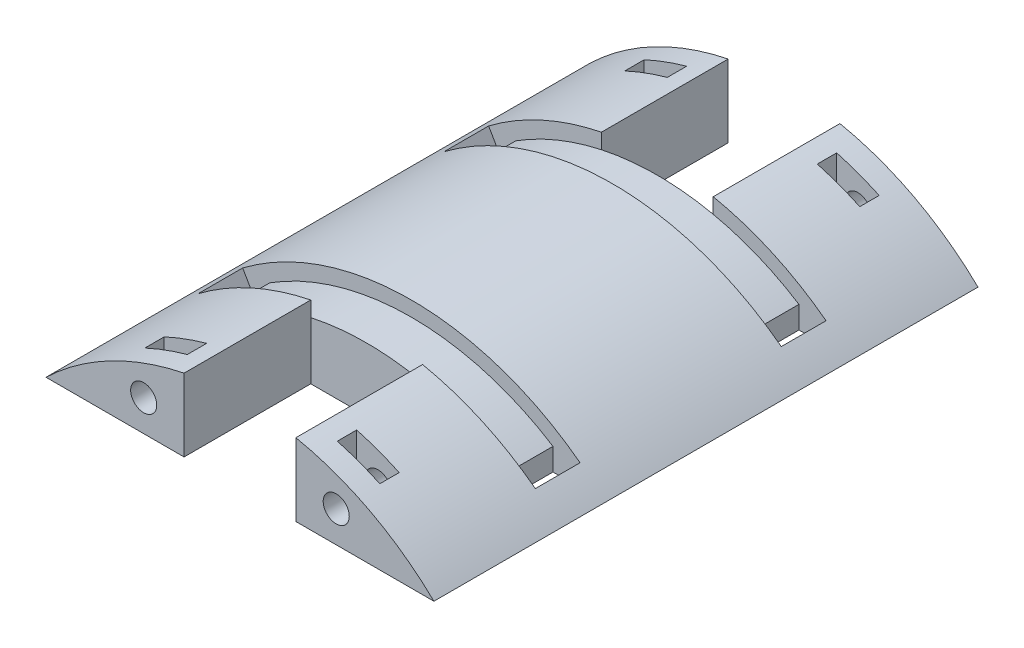
SolidWorks part; units mm, degrees
ref_plane "Plan de face" through (0, 0, 0) normal (0, 0, 1) x (1, 0, 0)
ref_plane "Plan de dessus" through (0, 0, 0) normal (0, 1, 0) x (1, 0, 0)
ref_plane "Plan de droite" through (0, 0, 0) normal (1, 0, 0) x (0, 0, -1)
sketch "Esquisse3" plane through (0, 0, 0) normal (0, 0, 1) x (1, 0, 0)
  line L0 (-13.0767, 27) -> (-26.024, 27)
  line L1 (13.0767, 27) -> (26.024, 27)
  line L2 (-13.0767, 27) -> (13.0767, 27)
  line L3 (-26.024, 27) -> (26.024, 27) construction
  line L4 (-26.024, 27) -> (-26.024, 0) construction
  line L5 (-26.024, 0) -> (26.024, 0) construction
  line L6 (26.024, 27) -> (26.024, 0) construction
  line L7 (8.9994, 41.4168) -> (9.1038, 41.3823)
  circle A0 centre (0, 0) radius 37.5 construction
  circle A1 centre (0, 0) radius 30 construction
  arc A2 (-26.024, 27) -> (26.024, 27) centre (0, 0) cw
  point P5 (0, 0)
  point P15 (0, 27)
  dimension "D1" = 75
  dimension "D2" = 60
  dimension "D4" = 27
extrude "Boss.-Extru.2" add sketch "Esquisse3" along normal blind 73 contours A2 L0 L2 L1 region at (0, 31.2549, 0)
sketch "Esquisse7" plane through (0, 0, 73) normal (0, 0, 1) x (1, 0, 0)
  line L0 (0, 33.75) -> (0, 0) construction
  line L1 (0, 0) -> (-12.9156, 31.1809) construction
  line L2 (0, 0) -> (12.9156, 31.1809) construction
  line L3 (-30, 0) -> (-37.5, 0) construction
  circle A0 centre (0, 0) radius 33.75 construction
  circle A2 centre (-12.9156, 31.1809) radius 1.75
  circle A3 centre (12.9156, 31.1809) radius 1.75
  circle A4 centre (0, 0) radius 37.5 construction
  circle A5 centre (0, 0) radius 30 construction
  arc A6 (26.024, 27) -> (-26.024, 27) centre (0, 0) ccw construction
  point P15 (-33.75, 0)
  dimension "D1" = 60
  dimension "D2" = 3.5
  dimension "D3" = 22.5
  dimension "D4" = 22.5
extrude "Enlèv. mat.-Extru.4" cut sketch "Esquisse7" against normal blind 12
sketch "Esquisse11" plane through (0, 0, 73) normal (0, 0, 1) x (1, 0, 0)
  line L0 (-12.9156, 31.1809) -> (-15.7656, 31.1809) construction
  line L1 (-15.7656, 31.1809) -> (-15.7656, 34.0249)
  line L2 (-15.7656, 31.1809) -> (-15.7656, 29.4264)
  line L3 (-15.7656, 29.4264) -> (-12.9156, 27.7809)
  line L4 (-12.9156, 27.7809) -> (-10.0656, 29.4264)
  line L5 (-10.0656, 29.4264) -> (-10.0656, 36.1239)
  line L6 (10.0656, 36.1239) -> (10.0656, 29.4264)
  line L7 (10.0656, 29.4264) -> (12.9156, 27.7809)
  line L8 (12.9156, 27.7809) -> (15.7656, 29.4264)
  line L9 (15.7656, 29.4264) -> (15.7656, 34.0249)
  line L10 (12.9156, 31.1809) -> (15.7656, 31.1809) construction
  line L11 (12.9156, 31.1809) -> (10.0656, 31.1809) construction
  line L12 (12.9156, 31.1809) -> (12.9156, 27.7809) construction
  line L13 (11.1341, 33.0694) -> (11.2201, 33.0694) construction
  arc A1 (26.024, 27) -> (-26.024, 27) centre (0, 0) ccw construction
  arc A2 (-15.7656, 34.0249) -> (-10.0656, 36.1239) centre (0, 0) cw
  arc A3 (10.0656, 36.1239) -> (15.7656, 34.0249) centre (0, 0) cw
  dimension "D1" = 5.7
  dimension "D2" = 120
  dimension "D3" = 3.4
  dimension "D4" = 5.7
  dimension "D5" = 3.4
  dimension "D6" = 120
extrude "Enlèv. mat.-Extru.5" cut sketch "Esquisse11" against normal blind 2.6 from offset 3 offset against normal yes
sketch "Esquisse12" plane through (0, 0, 0) normal (0, 0, -1) x (-1, 0, 0)
  line L0 (0, 0) -> (0, 33.75) construction
  line L1 (0, 0) -> (-12.9156, 31.1809) construction
  line L2 (0, 0) -> (12.9156, 31.1809) construction
  line L3 (-30, 0) -> (-37.5, 0) construction
  circle A0 centre (0, 0) radius 33.75 construction
  circle A1 centre (-12.9156, 31.1809) radius 1.75
  circle A2 centre (12.9156, 31.1809) radius 1.75
  circle A3 centre (0, 0) radius 37.5 construction
  circle A4 centre (0, 0) radius 30 construction
  arc A5 (26.024, 27) -> (-26.024, 27) centre (0, 0) ccw construction
  point P12 (-33.75, 0)
  dimension "D3" = 60
  dimension "D4" = 3.5
  dimension "D1" = 22.5
  dimension "D2" = 22.5
extrude "Enlèv. mat.-Extru.6" cut sketch "Esquisse12" against normal blind 12
sketch "Esquisse14" plane through (0, 0, 0) normal (0, 0, -1) x (-1, 0, 0)
  line L0 (-14.6656, 31.1809) -> (-11.1656, 31.1809) construction
  line L1 (-15.7656, 31.6891) -> (-15.7656, 34.0249)
  line L2 (-15.7656, 31.6891) -> (-15.7656, 29.4264)
  line L3 (-15.7656, 29.4264) -> (-12.9156, 27.7809)
  line L4 (-12.9156, 27.7809) -> (-10.0656, 29.4264)
  line L5 (-10.0656, 29.4264) -> (-10.0656, 36.1239)
  line L6 (10.0656, 36.1239) -> (10.0656, 29.4264)
  line L7 (10.0656, 29.4264) -> (12.9156, 27.7809)
  line L8 (12.9156, 27.7809) -> (15.7656, 29.4264)
  line L9 (15.7656, 29.4264) -> (15.7656, 34.0249)
  line L10 (11.1656, 31.1809) -> (14.6656, 31.1809) construction
  line L11 (-12.9156, 32.9309) -> (-12.9156, 29.4309) construction
  line L12 (-11.1656, 31.1809) -> (-10.0656, 31.1809) construction
  line L13 (-14.6656, 31.1809) -> (-15.7656, 31.1809) construction
  line L14 (12.9156, 32.9309) -> (12.9156, 29.4309) construction
  circle A1 centre (-12.9156, 31.1809) radius 1.75 construction
  arc A2 (-15.7656, 34.0249) -> (-10.0656, 36.1239) centre (0, 0) cw
  arc A3 (10.0656, 36.1239) -> (15.7656, 34.0249) centre (0, 0) cw
  arc A4 (26.024, 27) -> (-26.024, 27) centre (0, 0) ccw construction
  circle A5 centre (-12.9156, 31.1809) radius 1.75 construction
  circle A7 centre (12.9156, 31.1809) radius 1.75 construction
  circle A8 centre (12.9156, 31.1809) radius 1.75 construction
  point P29 (-12.9156, 31.1809)
  point P38 (12.9156, 31.1809)
  dimension "D1" = 5.7
  dimension "D6" = 3.4
  dimension "D2" = 120
  dimension "D3" = 3.4
  dimension "D4" = 5.7
  dimension "D5" = 120
extrude "Enlèv. mat.-Extru.7" cut sketch "Esquisse14" against normal blind 2.6 from offset 3 offset against normal yes
sketch "Esquisse21" plane through (0, 27, 0) normal (0, -1, 0) x (1, 0, 0)
  line L0 (-26.024, 73) -> (26.024, 73) construction
  line L1 (-7.5, 73) -> (7.5, 73)
  line L2 (-7.5, 73) -> (-7.5, 56)
  line L3 (-7.5, 56) -> (7.5, 56)
  line L4 (7.5, 73) -> (7.5, 56)
  line L5 (-26.024, 0) -> (26.024, 0) construction
  line L6 (-7.5, 0) -> (7.5, 0)
  line L7 (-7.5, 0) -> (-7.5, 17)
  line L8 (-7.5, 17) -> (7.5, 17)
  line L9 (7.5, 0) -> (7.5, 17)
  point P12 (0, 56)
  point P13 (0, 17)
  dimension "D1" = 17
  dimension "D2" = 15
extrude "Enlèv. mat.-Extru.14" cut sketch "Esquisse21" against normal through all
sketch "Esquisse22" plane through (0, 27, 0) normal (0, -1, 0) x (1, 0, 0)
  line L0 (-19, 50) -> (19, 50) construction
  line L1 (-21, 56) -> (-19, 56)
  line L2 (-21, 56) -> (-21, 50)
  line L3 (-21, 50) -> (-19, 50)
  line L4 (-19, 56) -> (-19, 50)
  line L5 (19, 56) -> (21, 56)
  line L6 (19, 56) -> (19, 50)
  line L7 (19, 50) -> (21, 50)
  line L8 (21, 56) -> (21, 50)
  line L9 (-21, 23) -> (-19, 23)
  line L10 (-21, 23) -> (-21, 17)
  line L11 (-21, 17) -> (-19, 17)
  line L12 (-19, 23) -> (-19, 17)
  line L13 (19, 23) -> (21, 23)
  line L14 (19, 23) -> (19, 17)
  line L15 (19, 17) -> (21, 17)
  line L16 (21, 23) -> (21, 17)
  line L17 (19, 50) -> (19, 23) construction
  line L18 (0, 56) -> (0, 17) construction
  line L19 (-7.5, 56) -> (7.5, 56) construction
  line L20 (7.5, 17) -> (-7.5, 17) construction
  line L21 (-7.5, 73) -> (-26.024, 73) construction
  point P16 (0, 50)
  point P24 (0, 36.5)
  point P25 (19, 36.5)
  dimension "D1" = 6
  dimension "D2" = 2
  dimension "D3" = 38
  dimension "D4" = 17
extrude "Enlèv. mat.-Extru.15" cut sketch "Esquisse22" against normal through all
sketch "Esquisse23" plane through (0, 0, 0) normal (0, 0, -1) x (-1, 0, 0)
  line L0 (-35.5, 0) -> (-37.5, 0) construction
  line L1 (-19, 29.9875) -> (-19, 32.3303)
  line L2 (19, 32.3303) -> (19, 29.9875)
  line L5 (-19, 29.9875) -> (19, 29.9875) construction
  circle A0 centre (0, 0) radius 37.5 construction
  circle A1 centre (0, 0) radius 35.5 construction
  arc A2 (-19, 29.9875) -> (19, 29.9875) centre (0, 0) cw
  arc A3 (-19, 32.3303) -> (19, 32.3303) centre (0, 0) cw
  arc A4 (7.5, 36.7423) -> (-7.5, 36.7423) centre (0, 0) ccw construction
  point P11 (0, 29.9875)
  dimension "D2" = 38
  dimension "D1" = 2
extrude "Enlèv. mat.-Extru.17" cut sketch "Esquisse23" against normal blind 6 from offset 17 offset against normal yes
sketch "Esquisse27" plane through (0, 0, 73) normal (0, 0, 1) x (1, 0, 0)
  line L0 (-37.5, 0) -> (-35.5, 0) construction
  line L1 (-19, 32.3303) -> (-19, 29.9875)
  line L2 (19, 32.3303) -> (19, 29.9875)
  line L3 (-19, 29.9875) -> (19, 29.9875) construction
  circle A0 centre (0, 0) radius 37.5 construction
  circle A1 centre (0, 0) radius 35.5 construction
  arc A2 (-7.5, 36.7423) -> (-26.024, 27) centre (0, 0) ccw construction
  arc A3 (19, 32.3303) -> (-19, 32.3303) centre (0, 0) ccw
  arc A4 (19, 29.9875) -> (-19, 29.9875) centre (0, 0) ccw
  point P13 (0, 29.9875)
  dimension "D1" = 2
  dimension "D2" = 38
extrude "Enlèv. mat.-Extru.19" cut sketch "Esquisse27" against normal blind 6 from offset 17 offset against normal yes
chamfer "Chanfrein1" distance 4 angle 30 2 edges at (21, 31.0685, 20) (21, 31.0685, 53) first distance on face at (21, 29.0342, 20) first distance on face at (21, 29.0342, 53)
chamfer "Chanfrein2" distance 4 angle 30 2 edges at (-21, 31.0685, 20) (-21, 31.0685, 53) first distance on face at (-21, 29.0342, 20) first distance on face at (-21, 29.0342, 53)
